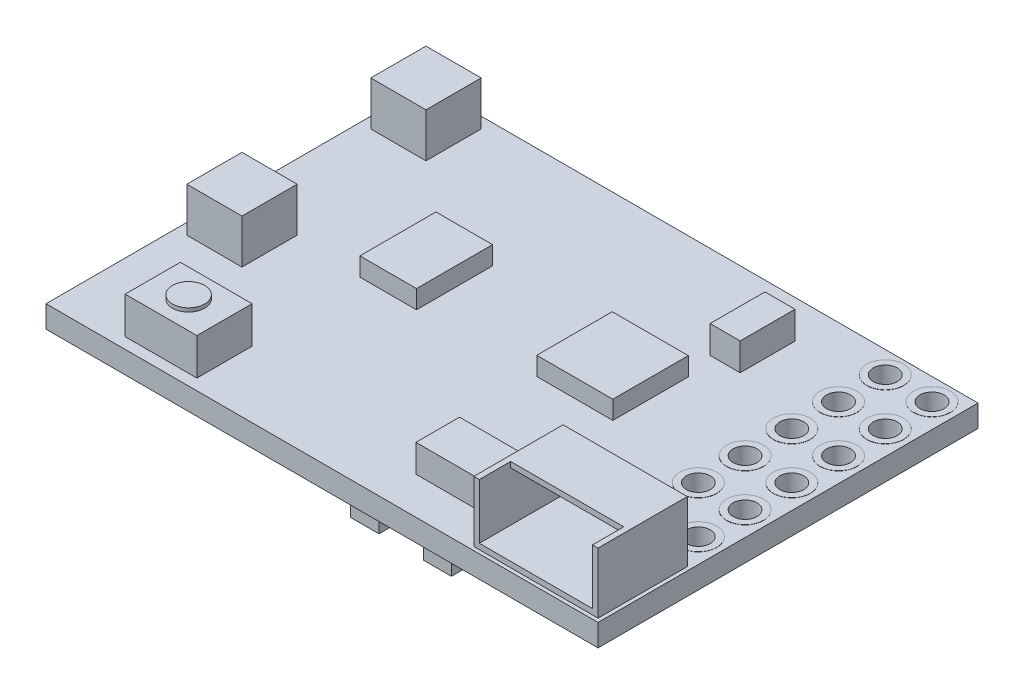
SolidWorks part; units mm, degrees
ref_plane "Front Plane" through (0, 0, 0) normal (0, 0, 1) x (1, 0, 0)
ref_plane "Top Plane" through (0, 0, 0) normal (0, 1, 0) x (1, 0, 0)
ref_plane "Right Plane" through (0, 0, 0) normal (1, 0, 0) x (0, 0, -1)
sketch "Sketch1" plane through (0, 0, 0) normal (0, 1, 0) x (1, 0, 0)
  line L1 (-15, 10.325) -> (15, 10.325)
  line L2 (-15, 10.325) -> (-15, -10.325)
  line L3 (-15, -10.325) -> (15, -10.325)
  line L4 (15, 10.325) -> (15, -10.325)
  line L5 (-15, 10.325) -> (15, -10.325) construction
  line L6 (-15, -10.325) -> (15, 10.325) construction
  point P0 (0, 0)
  dimension "D1" = 30
  dimension "D2" = 20.65
extrude "Boss-Extrude1" add sketch "Sketch1" along normal blind 1.2
sketch "Sketch2" plane through (0, 1.2, 0) normal (0, 1, 0) x (1, 0, 0)
  line L0 (13.7, 10.325) -> (13.7, -10.325) construction
  line L1 (15, 10.325) -> (-15, 10.325) construction
  line L2 (-15, -10.325) -> (15, -10.325) construction
  line L3 (11.16, 9.125) -> (13.7, 9.125) construction
  line L4 (15, -10.325) -> (15, 10.325) construction
  line L5 (13.7, 9.125) -> (13.7, 6.585) construction
  circle A0 centre (13.7, 9.125) radius 0.65
  circle A1 centre (11.16, 9.125) radius 0.65
  circle A2 centre (11.16, 6.585) radius 0.65
  circle A3 centre (11.16, 4.045) radius 0.65
  circle A4 centre (11.16, 1.505) radius 0.65
  circle A5 centre (11.16, -1.035) radius 0.65
  circle A6 centre (11.16, -3.575) radius 0.65
  circle A7 centre (13.7, 6.585) radius 0.65
  circle A8 centre (13.7, 4.045) radius 0.65
  circle A9 centre (13.7, 1.505) radius 0.65
  circle A10 centre (13.7, -1.035) radius 0.65
  circle A11 centre (13.7, -3.575) radius 0.65
  dimension "D3" = 1.3
  dimension "D1" = 1.3
  dimension "D2" = 2
  dimension "D4" = 1.2
  dimension "D6" = 2.54
  dimension "D5" = 6
extrude "Cut-Extrude1" cut sketch "Sketch2" against normal up to next
sketch "Sketch3" plane through (0, 1.2, 0) normal (0, 1, 0) x (1, 0, 0)
  line L0 (-15, -10.325) -> (15, -10.325) construction
  line L1 (14.8, -10.125) -> (8.05, -10.125)
  line L2 (14.8, -10.125) -> (14.8, -5.275)
  line L3 (14.8, -5.275) -> (8.05, -5.275)
  line L4 (8.05, -10.125) -> (8.05, -5.275)
  line L5 (15, -10.325) -> (15, 10.325) construction
  dimension "D1" = 6.75
  dimension "D2" = 4.85
  dimension "D3" = 0.2
  dimension "D4" = 0.2
extrude "Boss-Extrude2" add sketch "Sketch3" along normal blind 3.3
sketch "Sketch4" plane through (0, 1.2, 0) normal (0, 1, 0) x (1, 0, 0)
  line L0 (15, 10.325) -> (-15, 10.325) construction
  line L1 (-14.4, 9.725) -> (-11.4, 9.725)
  line L2 (-14.4, 9.725) -> (-14.4, 6.725)
  line L3 (-14.4, 6.725) -> (-11.4, 6.725)
  line L4 (-11.4, 9.725) -> (-11.4, 6.725)
  line L5 (-15, 10.325) -> (-15, -10.325) construction
  line L6 (-15, 3.225) -> (15, 3.225) construction
  line L7 (15, -10.325) -> (15, 10.325) construction
  line L8 (-14.4, -0.275) -> (-11.4, -0.275)
  line L9 (-11.4, -3.275) -> (-11.4, -0.275)
  line L10 (-14.4, -3.275) -> (-11.4, -3.275)
  line L11 (-14.4, -3.275) -> (-14.4, -0.275)
  dimension "D1" = 3
  dimension "D2" = 3
  dimension "D3" = 0.6
  dimension "D4" = 0.6
  dimension "D5" = 7
extrude "Boss-Extrude3" add sketch "Sketch4" along normal blind 2.4
sketch "Sketch5" plane through (0, 1.2, 0) normal (0, 1, 0) x (1, 0, 0)
  line L0 (-15, 10.325) -> (-15, -10.325) construction
  line L1 (-11.3, -9.725) -> (-7.4, -9.725)
  line L2 (-11.3, -9.725) -> (-11.3, -6.725)
  line L3 (-11.3, -6.725) -> (-7.4, -6.725)
  line L4 (-7.4, -9.725) -> (-7.4, -6.725)
  line L5 (-15, -10.325) -> (15, -10.325) construction
  dimension "D1" = 3.9
  dimension "D2" = 3
  dimension "D3" = 3.7
  dimension "D4" = 0.6
extrude "Boss-Extrude4" add sketch "Sketch5" along normal blind 2
sketch "Sketch6" plane through (0, 3.2, 0) normal (0, 1, 0) x (1, 0, 0)
  line L0 (-11.3, -8.225) -> (-7.4, -8.225) construction
  line L1 (-11.3, -6.725) -> (-11.3, -9.725) construction
  line L2 (-7.4, -9.725) -> (-7.4, -6.725) construction
  line L3 (-9.35, -6.725) -> (-9.35, -9.725) construction
  line L4 (-7.4, -6.725) -> (-11.3, -6.725) construction
  line L5 (-11.3, -9.725) -> (-7.4, -9.725) construction
  circle A0 centre (-9.35, -8.225) radius 0.875
  dimension "D1" = 1.75
extrude "Boss-Extrude5" add sketch "Sketch6" along normal blind 0.2
sketch "Sketch7" plane through (0, 4.5, 0) normal (0, 1, 0) x (1, 0, 0)
  line L0 (11.425, -5.275) -> (11.425, -10.125) construction
  line L1 (14.8, -5.275) -> (8.05, -5.275) construction
  line L2 (8.05, -10.125) -> (14.8, -10.125) construction
  line L3 (8.05, -10.125) -> (14.8, -10.125) construction
  line L4 (8.35, -10.125) -> (14.5, -10.125)
  line L5 (8.35, -10.125) -> (8.35, -8.425)
  line L6 (8.35, -8.425) -> (14.5, -8.425)
  line L7 (14.5, -10.125) -> (14.5, -8.425)
  line L8 (8.05, -5.275) -> (8.05, -10.125) construction
  point P12 (11.425, -8.425)
  dimension "D1" = 0.3
  dimension "D2" = 1.7
extrude "Cut-Extrude2" cut sketch "Sketch7" against normal offset from surface (3 mm away) 0.3 up to face at (11.16, 1.2, 4.225)
sketch "Sketch8" plane through (0, 0, 8.425) normal (0, 0, 1) x (1, 0, 0)
  line L0 (14.5, 1.5) -> (14.5, 4.5) construction
  line L1 (8.35, 1.5) -> (14.5, 1.5)
  line L2 (8.35, 1.5) -> (8.35, 4.2)
  line L3 (8.35, 4.2) -> (14.5, 4.2)
  line L4 (14.5, 1.5) -> (14.5, 4.2)
  line L5 (14.5, 4.5) -> (8.35, 4.5) construction
  dimension "D1" = 0.3
extrude "Cut-Extrude3" cut sketch "Sketch8" against normal offset from surface (2.85 mm away) 0.3 up to face at (11.425, 2.85, 5.275)
sketch "Sketch9" plane through (0, 1.2, 0) normal (0, 1, 0) x (1, 0, 0)
  line L1 (5.896, 3.685) -> (1.7624, 3.685)
  line L2 (5.896, 3.685) -> (5.896, -0.4166)
  line L3 (5.896, -0.4166) -> (1.7624, -0.4166)
  line L4 (1.7624, 3.685) -> (1.7624, -0.4166)
  line L5 (-7.7224, 3.5888) -> (-4.6463, 3.5888)
  line L6 (-7.7224, 3.5888) -> (-7.7224, -0.5447)
  line L7 (-7.7224, -0.5447) -> (-4.6463, -0.5447)
  line L8 (-4.6463, 3.5888) -> (-4.6463, -0.5447)
extrude "Boss-Extrude6" add sketch "Sketch9" along normal blind 1
sketch "Sketch10" plane through (0, 1.2, 0) normal (0, 1, 0) x (1, 0, 0)
  line L1 (7.1136, 8.2672) -> (5.4794, 8.2672)
  line L2 (7.1136, 8.2672) -> (7.1136, 5.2871)
  line L3 (7.1136, 5.2871) -> (5.4794, 5.2871)
  line L4 (5.4794, 8.2672) -> (5.4794, 5.2871)
  line L5 (7.5302, -5.928) -> (3.0762, -5.928)
  line L6 (7.5302, -5.928) -> (7.5302, -8.2992)
  line L7 (7.5302, -8.2992) -> (3.0762, -8.2992)
  line L8 (3.0762, -5.928) -> (3.0762, -8.2992)
extrude "Boss-Extrude7" add sketch "Sketch10" along normal blind 1.5
sketch "Sketch11" plane through (0, 0, 0) normal (0, -1, 0) x (1, 0, 0)
  line L1 (-6.3538, 2.621) -> (0.4959, 2.621)
  line L2 (-6.3538, 2.621) -> (-6.3538, -4.2287)
  line L3 (-6.3538, -4.2287) -> (0.4959, -4.2287)
  line L4 (0.4959, 2.621) -> (0.4959, -4.2287)
  line L6 (-15, -10.325) -> (-15, 10.325) construction
  line L7 (6.1467, 9.4396) -> (4.628, 9.4396)
  line L8 (6.1467, 9.4396) -> (6.1467, 6.4332)
  line L9 (6.1467, 6.4332) -> (4.628, 6.4332)
  line L10 (4.628, 9.4396) -> (4.628, 6.4332)
  line L11 (2.1795, 9.4086) -> (0.6298, 9.4086)
  line L12 (2.1795, 9.4086) -> (2.1795, 6.3402)
  line L13 (2.1795, 6.3402) -> (0.6298, 6.3402)
  line L14 (0.6298, 9.4086) -> (0.6298, 6.3402)
  line L15 (4.9689, 5.6274) -> (6.1467, 5.6274)
  line L16 (4.9689, 5.6274) -> (4.9689, 2.8689)
  line L17 (4.9689, 2.8689) -> (6.1467, 2.8689)
  line L18 (6.1467, 5.6274) -> (6.1467, 2.8689)
  line L19 (-15, -4.3837) -> (-12.1398, -4.3837)
  line L20 (-15, -4.3837) -> (-15, -8.5679)
  line L21 (-15, -8.5679) -> (-12.1398, -8.5679)
  line L22 (-12.1398, -4.3837) -> (-12.1398, -8.5679)
  line L23 (-13.5965, 3.7987) -> (-11.21, 3.7987)
  line L24 (-13.5965, 3.7987) -> (-13.5965, 0.6993)
  line L25 (-13.5965, 0.6993) -> (-11.21, 0.6993)
  line L26 (-11.21, 3.7987) -> (-11.21, 0.6993)
  line L27 (-10.0012, -6.3053) -> (-8.7304, -6.3053)
  line L28 (-10.0012, -6.3053) -> (-10.0012, -9.4667)
  line L29 (-10.0012, -9.4667) -> (-8.7304, -9.4667)
  line L30 (-8.7304, -6.3053) -> (-8.7304, -9.4667)
extrude "Boss-Extrude8" add sketch "Sketch11" along normal blind 1.5
sketch "Sketch12" plane through (0, 1.2, 0) normal (0, 1, 0) x (1, 0, 0)
  circle A0 centre (11.16, 9.125) radius 1
  circle A1 centre (13.7, 9.125) radius 1
  circle A2 centre (13.7, 6.585) radius 1
  circle A3 centre (11.16, 6.585) radius 1
  circle A4 centre (11.16, 4.045) radius 1
  circle A5 centre (13.7, 4.045) radius 1
  circle A6 centre (13.7, 1.505) radius 1
  circle A7 centre (11.16, 1.505) radius 1
  circle A8 centre (11.16, -1.035) radius 1
  circle A9 centre (11.16, -3.575) radius 1
  circle A10 centre (13.7, -3.575) radius 1
  circle A11 centre (13.7, -1.035) radius 1
  circle A12 centre (11.16, -3.575) radius 0.65 construction
  circle A13 centre (13.7, -3.575) radius 0.65 construction
  circle A14 centre (13.7, -1.035) radius 0.65 construction
  circle A15 centre (11.16, -1.035) radius 0.65 construction
  circle A16 centre (11.16, 1.505) radius 0.65 construction
  circle A17 centre (13.7, 1.505) radius 0.65 construction
  circle A18 centre (13.7, 4.045) radius 0.65 construction
  circle A19 centre (11.16, 4.045) radius 0.65 construction
  circle A20 centre (11.16, 6.585) radius 0.65 construction
  circle A21 centre (13.7, 6.585) radius 0.65 construction
  circle A22 centre (13.7, 9.125) radius 0.65 construction
  circle A23 centre (11.16, 9.125) radius 0.65 construction
  circle A24 centre (11.16, -3.575) radius 0.65
  circle A25 centre (13.7, -3.575) radius 0.65
  circle A26 centre (13.7, -1.035) radius 0.65
  circle A27 centre (11.16, -1.035) radius 0.65
  circle A28 centre (11.16, 1.505) radius 0.65
  circle A29 centre (13.7, 1.505) radius 0.65
  circle A30 centre (13.7, 4.045) radius 0.65
  circle A31 centre (11.16, 4.045) radius 0.65
  circle A32 centre (11.16, 6.585) radius 0.65
  circle A33 centre (13.7, 6.585) radius 0.65
  circle A34 centre (13.7, 9.125) radius 0.65
  circle A35 centre (11.16, 9.125) radius 0.65
  dimension "D1" = 2
extrude "Boss-Extrude9" add sketch "Sketch12" along normal blind 0.01
ref_plane "Plane1" through (0, 0.6, 0) normal (0, 1, 0) x (1, 0, 0)
mirror "Mirror1" about plane through (0, 0.6, 0) normal (0, 1, 0) of "Boss-Extrude9"
